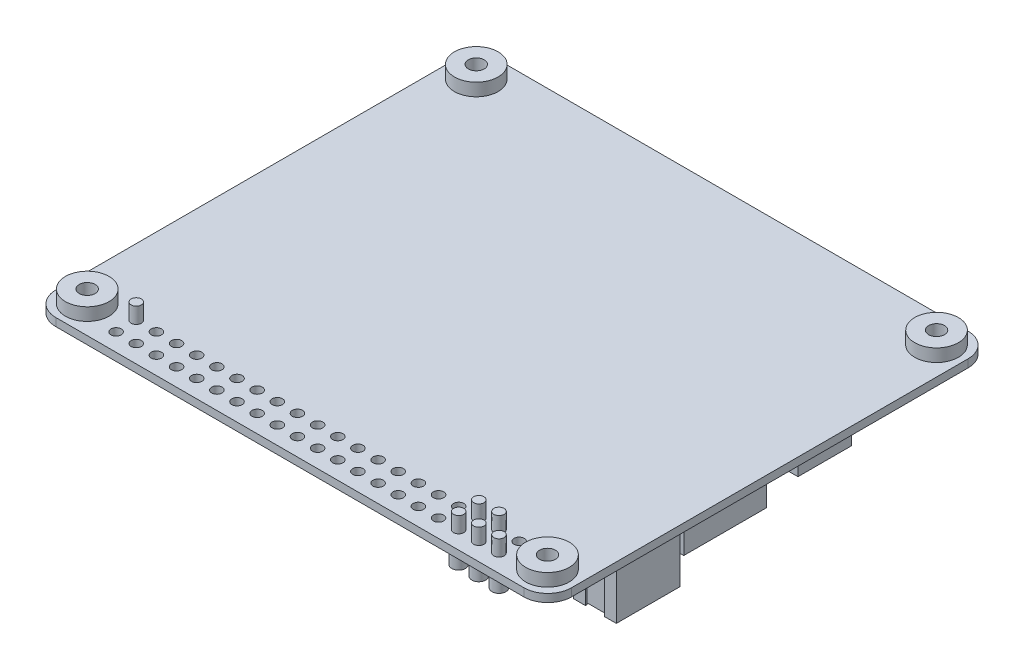
SolidWorks part; units mm, degrees
ref_plane "前视基准面" through (0, 0, 0) normal (0, 0, 1) x (1, 0, 0)
ref_plane "上视基准面" through (0, 0, 0) normal (0, 1, 0) x (1, 0, 0)
ref_plane "右视基准面" through (0, 0, 0) normal (1, 0, 0) x (0, 0, -1)
sketch "草图1" plane through (0, 0, 0) normal (0, 1, 0) x (1, 0, 0)
  line L1 (32.5, -28) -> (-32.5, -28)
  line L2 (32.5, -28) -> (32.5, 28)
  line L3 (32.5, 28) -> (-32.5, 28)
  line L4 (-32.5, -28) -> (-32.5, 28)
  line L5 (32.5, -28) -> (-32.5, 28) construction
  line L6 (32.5, 28) -> (-32.5, -28) construction
  point P0 (0, 0)
  dimension "D1" = 56
  dimension "D2" = 65
extrude "凸台-拉伸1" add sketch "草图1" along normal blind 1
fillet "圆角1" radius 3 4 edges at (32.5, 0.5, -28) (32.5, 0.5, 28) (-32.5, 0.5, 28) (-32.5, 0.5, -28)
sketch "草图2" plane through (0, 1, 0) normal (0, 1, 0) x (1, 0, 0)
  circle A0 centre (-29.0307, 24.5287) radius 2.75
  circle A1 centre (28.9808, 24.5287) radius 2.75
  circle A2 centre (-29.0307, -24.5065) radius 2.75
  circle A3 centre (28.9808, -24.5065) radius 2.75
  dimension "D1" = 5.5
extrude "凸台-拉伸2" add sketch "草图2" along normal blind 1.6
sketch "草图3" plane through (0, 2.6, 0) normal (0, 1, 0) x (1, 0, 0)
  circle A0 centre (-29.0307, 24.5287) radius 1
  circle A1 centre (28.9808, 24.5287) radius 1
  circle A2 centre (-29.0307, -24.5065) radius 1
  circle A3 centre (28.9808, -24.5065) radius 1
  dimension "D1" = 2
extrude "切除-拉伸1" cut sketch "草图3" against normal up to next
sketch "草图4" plane through (0, 0, 0) normal (0, -1, 0) x (1, 0, 0)
  line L0 (29.5, -28) -> (-29.5, -28) construction
  line L1 (25.5, -28) -> (16.5, -28)
  line L2 (25.5, -28) -> (25.5, -20.6)
  line L3 (25.5, -20.6) -> (16.5, -20.6)
  line L4 (16.5, -28) -> (16.5, -20.6)
  line L5 (32.5, 25) -> (32.5, -25) construction
  dimension "D1" = 7.4
  dimension "D2" = 9
  dimension "D3" = 7
extrude "凸台-拉伸3" add sketch "草图4" along normal blind 3.2
sketch "草图5" plane through (0, 0, -28) normal (0, 0, -1) x (-1, 0, 0)
  line L0 (-29.5, 0) -> (-25.5, 0) construction
  line L1 (-16.5, -3.2) -> (-25.5, -3.2)
  line L2 (-16.5, -3.2) -> (-16.5, 0)
  line L3 (-16.5, 0) -> (-25.5, 0)
  line L4 (-25.5, -3.2) -> (-25.5, 0)
  line L5 (-25.5, -3.2) -> (-25.5, 0) construction
extrude "凸台-拉伸4" add sketch "草图5" along normal blind 1
fillet "圆角3" radius 1 4 edges at (25.5, 0, -28.5) (25.5, -3.2, -24.8) (16.5, -3.2, -24.8) (16.5, 0, -28.5)
sketch "草图6" plane through (0, 0, 0) normal (0, -1, 0) x (1, 0, 0)
  line L0 (-32.5, -25) -> (-32.5, 25) construction
  circle A0 centre (-17.5, 0) radius 7
  dimension "D1" = 14
  dimension "D2" = 15
extrude "凸台-拉伸5" add sketch "草图6" along normal blind 2
sketch "草图8" plane through (0, 0, 0) normal (0, -1, 0) x (1, 0, 0)
  circle A0 centre (28.9808, 24.5065) radius 2
  circle A1 centre (28.9808, -24.5287) radius 2
  circle A2 centre (-29.0307, -24.5287) radius 2
  circle A3 centre (-29.0307, 24.5065) radius 2
  dimension "D1" = 4
extrude "凸台-拉伸6" add sketch "草图8" along normal blind 0.5
sketch "草图9" plane through (0, 0, 0) normal (0, 1, 0) x (1, 0, 0)
  circle A0 centre (-29.0307, 24.5287) radius 1
  circle A1 centre (28.9808, 24.5287) radius 1
  circle A2 centre (-29.0307, -24.5065) radius 1
  circle A3 centre (28.9808, -24.5065) radius 1
  circle A4 centre (28.9808, -24.5065) radius 2 construction
  circle A5 centre (28.9808, 24.5287) radius 2 construction
  circle A6 centre (-29.0307, -24.5065) radius 2 construction
  circle A7 centre (-29.0307, 24.5287) radius 2 construction
extrude "切除-拉伸2" cut sketch "草图9" against normal up to next
sketch "草图10" plane through (0, 0, -29) normal (0, 0, -1) x (-1, 0, 0)
  line L8 (-17.5, -0.2) -> (-24.5, -0.2)
  line L9 (-25.3, -1) -> (-25.3, -2.2)
  line L10 (-24.5, -3) -> (-17.5, -3)
  line L11 (-16.7, -2.2) -> (-16.7, -1)
  line L12 (-17.5, -0.2) -> (-24.5, -0.2)
  line L13 (-25.3, -1) -> (-25.3, -2.2)
  line L14 (-24.5, -3) -> (-17.5, -3)
  line L15 (-16.7, -2.2) -> (-16.7, -1)
  arc A8 (-24.5, -0.2) -> (-25.3, -1) centre (-24.5, -1) ccw
  arc A9 (-25.3, -2.2) -> (-24.5, -3) centre (-24.5, -2.2) ccw
  arc A10 (-17.5, -3) -> (-16.7, -2.2) centre (-17.5, -2.2) ccw
  arc A11 (-16.7, -1) -> (-17.5, -0.2) centre (-17.5, -1) ccw
  arc A12 (-24.5, -0.2) -> (-25.3, -1) centre (-24.5, -1) ccw
  arc A13 (-25.3, -2.2) -> (-24.5, -3) centre (-24.5, -2.2) ccw
  arc A14 (-17.5, -3) -> (-16.7, -2.2) centre (-17.5, -2.2) ccw
  arc A15 (-16.7, -1) -> (-17.5, -0.2) centre (-17.5, -1) ccw
  dimension "D1" = 0.2
extrude "切除-拉伸3" cut sketch "草图10" against normal blind 8
sketch "草图12" plane through (0, 0, 0) normal (0, -1, 0) x (1, 0, 0)
  line L0 (16.5, -28) -> (-29.5, -28) construction
  line L1 (-16.6, -28) -> (-23.9, -28)
  line L2 (-16.6, -28) -> (-16.6, -22.7)
  line L3 (-16.6, -22.7) -> (-23.9, -22.7)
  line L4 (-23.9, -28) -> (-23.9, -22.7)
  line L5 (-32.5, -25) -> (-32.5, 25) construction
  dimension "D1" = 7.3
  dimension "D2" = 8.6
  dimension "D3" = 5.3
extrude "凸台-拉伸8" add sketch "草图12" along normal blind 2.4
sketch "草图13" plane through (0, 0, -28) normal (0, 0, -1) x (-1, 0, 0)
  line L1 (23.9, -2.4) -> (16.6, -2.4)
  line L2 (23.9, -2.4) -> (23.9, 0)
  line L3 (23.9, 0) -> (16.6, 0)
  line L4 (16.6, -2.4) -> (16.6, 0)
extrude "凸台-拉伸9" add sketch "草图13" along normal up to surface (1 mm away) up to face at (21, -1.6, -29)
chamfer "倒角1" distance 0.4 angle 45 2 edges at (-16.6, -2.4, -25.85) (-23.9, -2.4, -25.85)
chamfer "倒角2" distance 1 angle 45 2 edges at (-16.6, 0, -28.5) (-23.9, 0, -28.5)
sketch "草图14" plane through (0, 0, -29) normal (0, 0, -1) x (-1, 0, 0)
  line L16 (22.8172, -0.2) -> (17.6828, -0.2)
  line L17 (17.6828, -0.2) -> (16.8, -1.0828)
  line L18 (16.8, -1.0828) -> (16.8, -1.9172)
  line L19 (16.8, -1.9172) -> (17.0828, -2.2)
  line L20 (17.0828, -2.2) -> (23.4172, -2.2)
  line L21 (23.4172, -2.2) -> (23.7, -1.9172)
  line L22 (23.7, -1.9172) -> (23.7, -1.0828)
  line L23 (23.7, -1.0828) -> (22.8172, -0.2)
  line L24 (22.8172, -0.2) -> (17.6828, -0.2)
  line L25 (17.6828, -0.2) -> (16.8, -1.0828)
  line L26 (16.8, -1.0828) -> (16.8, -1.9172)
  line L27 (16.8, -1.9172) -> (17.0828, -2.2)
  line L28 (17.0828, -2.2) -> (23.4172, -2.2)
  line L29 (23.4172, -2.2) -> (23.7, -1.9172)
  line L30 (23.7, -1.9172) -> (23.7, -1.0828)
  line L31 (23.7, -1.0828) -> (22.8172, -0.2)
  dimension "D1" = 0.2
extrude "切除-拉伸4" cut sketch "草图14" against normal blind 2.4
sketch "草图17" plane through (0, 0, -28) normal (0, 0, -1) x (-1, 0, 0)
  line L0 (23.9, -1) -> (23.9, 0)
  line L1 (23.9, 0) -> (22.9, 0)
  line L2 (22.9, 0) -> (23.9, -1)
  line L3 (16.6, 0) -> (17.6, 0)
  line L4 (17.6, 0) -> (16.6, -1)
  line L5 (16.6, -1) -> (16.6, 0) construction
  line L6 (16.6, -1) -> (16.6, 0)
extrude "切除-拉伸5" cut sketch "草图17" against normal up to surface (5.3 mm away) up to face at (-20.25, -1.4667, -22.7)
fillet "圆角4" radius 0.2 1 edges at (-17.5, -2, -7)
sketch "草图19" plane through (0, 0, 0) normal (0, -1, 0) x (1, 0, 0)
  line L0 (32.5, 25) -> (32.5, -25) construction
  line L1 (32, 18.85) -> (26.6, 18.85)
  line L2 (32, 18.85) -> (32, 10.85)
  line L3 (32, 10.85) -> (26.6, 10.85)
  line L4 (26.6, 18.85) -> (26.6, 10.85)
  line L5 (-29.5, 28) -> (29.5, 28) construction
  dimension "D1" = 8
  dimension "D2" = 5.4
  dimension "D3" = 0.5
  dimension "D4" = 9.15
extrude "凸台-拉伸13" add sketch "草图19" along normal blind 6.22
sketch "草图20" plane through (0, -6.22, 0) normal (0, -1, 0) x (1, 0, 0)
  line L0 (30.5, 18.85) -> (30.5, 18.65)
  line L1 (32, 18.85) -> (26.6, 18.85) construction
  line L2 (30.5, 18.65) -> (31.3599, 18.65)
  line L3 (31.3599, 18.65) -> (31.3599, 18.45)
  line L4 (31.3599, 18.45) -> (26.9378, 18.45)
  line L5 (26.9378, 18.45) -> (26.9378, 18.65)
  line L6 (26.9378, 18.65) -> (28.1, 18.65)
  line L7 (28.1, 18.65) -> (28.1, 18.85)
  line L8 (32, 18.85) -> (26.6, 18.85) construction
  line L9 (28.1, 18.85) -> (30.5, 18.85)
  line L10 (30.5, 10.85) -> (30.5, 11.05)
  line L11 (26.6, 10.85) -> (32, 10.85) construction
  line L12 (30.5, 11.05) -> (31.3599, 11.05)
  line L13 (31.3599, 11.05) -> (31.3599, 11.25)
  line L14 (31.3599, 11.25) -> (26.9378, 11.25)
  line L15 (26.9378, 11.25) -> (26.9378, 11.05)
  line L16 (26.9378, 11.05) -> (28.1, 11.05)
  line L17 (28.1, 11.05) -> (28.1, 10.85)
  line L18 (28.1, 10.85) -> (30.5, 10.85)
  line L19 (32, 10.85) -> (32, 18.85) construction
  line L20 (26.6, 18.85) -> (26.6, 10.85) construction
  dimension "D1" = 0.2
  dimension "D2" = 0.2
  dimension "D3" = 0.2
  dimension "D4" = 1.5
  dimension "D5" = 1.5
extrude "切除-拉伸6" cut sketch "草图20" against normal blind 6.22
sketch "草图21" plane through (0, -6.22, 0) normal (0, -1, 0) x (1, 0, 0)
  line L1 (31.3599, 18.0753) -> (26.9378, 18.0753)
  line L2 (31.3599, 18.0753) -> (31.3599, 11.6247)
  line L3 (31.3599, 11.6247) -> (26.9378, 11.6247)
  line L4 (26.9378, 18.0753) -> (26.9378, 11.6247)
  line L5 (31.3599, 18.0753) -> (26.9378, 11.6247) construction
  line L6 (31.3599, 11.6247) -> (26.9378, 18.0753) construction
  point P0 (29.1489, 14.85)
extrude "切除-拉伸7" cut sketch "草图21" against normal blind 5
sketch "草图22" plane through (0, -1.22, 0) normal (0, -1, 0) x (1, 0, 0)
  line L1 (29.5742, 16.0721) -> (29.0742, 16.0721)
  line L2 (29.5742, 16.0721) -> (29.5742, 15.5721)
  line L3 (29.5742, 15.5721) -> (29.0742, 15.5721)
  line L4 (29.0742, 16.0721) -> (29.0742, 15.5721)
  line L5 (29.5742, 16.0721) -> (29.0742, 15.5721) construction
  line L6 (29.5742, 15.5721) -> (29.0742, 16.0721) construction
  line L7 (29.5566, 14.331) -> (29.0566, 14.331)
  line L8 (29.5566, 14.331) -> (29.5566, 13.831)
  line L9 (29.5566, 13.831) -> (29.0566, 13.831)
  line L10 (29.0566, 14.331) -> (29.0566, 13.831)
  line L11 (29.5566, 14.331) -> (29.0566, 13.831) construction
  line L12 (29.5566, 13.831) -> (29.0566, 14.331) construction
  point P0 (29.3242, 15.8221)
  point P5 (29.3066, 14.081)
  dimension "D1" = 0.5
extrude "凸台-拉伸14" add sketch "草图22" along normal blind 5
chamfer "倒角3" distance 0.1 angle 45 8 edges at (29.3066, -6.22, 14.331) (29.5566, -6.22, 14.081) (29.3066, -6.22, 13.831) (29.0566, -6.22, 14.081) (29.3242, -6.22, 16.0721) (29.5742, -6.22, 15.8221) (29.3242, -6.22, 15.5721) (29.0742, -6.22, 15.8221)
sketch "草图26" plane through (0, 0, 0) normal (0, -1, 0) x (1, 0, 0)
  circle A0 centre (24.13, 25.77) radius 0.65
  circle A40 centre (21.59, 25.77) radius 0.65
  circle A41 centre (19.05, 25.77) radius 0.65
  circle A42 centre (16.51, 25.77) radius 0.65
  circle A43 centre (13.97, 25.77) radius 0.65
  circle A44 centre (11.43, 25.77) radius 0.65
  circle A45 centre (8.89, 25.77) radius 0.65
  circle A46 centre (6.35, 25.77) radius 0.65
  circle A47 centre (3.81, 25.77) radius 0.65
  circle A48 centre (1.27, 25.77) radius 0.65
  circle A49 centre (-1.27, 25.77) radius 0.65
  circle A50 centre (-3.81, 25.77) radius 0.65
  circle A51 centre (-6.35, 25.77) radius 0.65
  circle A52 centre (-8.89, 25.77) radius 0.65
  circle A53 centre (-11.43, 25.77) radius 0.65
  circle A54 centre (-13.97, 25.77) radius 0.65
  circle A55 centre (-16.51, 25.77) radius 0.65
  circle A56 centre (-19.05, 25.77) radius 0.65
  circle A57 centre (-21.59, 25.77) radius 0.65
  circle A58 centre (-24.13, 25.77) radius 0.65
  circle A59 centre (21.59, 23.23) radius 0.65
  circle A60 centre (19.05, 23.23) radius 0.65
  circle A61 centre (16.51, 23.23) radius 0.65
  circle A62 centre (13.97, 23.23) radius 0.65
  circle A63 centre (11.43, 23.23) radius 0.65
  circle A64 centre (8.89, 23.23) radius 0.65
  circle A65 centre (6.35, 23.23) radius 0.65
  circle A66 centre (3.81, 23.23) radius 0.65
  circle A67 centre (1.27, 23.23) radius 0.65
  circle A68 centre (-1.27, 23.23) radius 0.65
  circle A69 centre (-3.81, 23.23) radius 0.65
  circle A70 centre (-6.35, 23.23) radius 0.65
  circle A71 centre (-8.89, 23.23) radius 0.65
  circle A72 centre (-11.43, 23.23) radius 0.65
  circle A73 centre (-13.97, 23.23) radius 0.65
  circle A74 centre (-16.51, 23.23) radius 0.65
  circle A75 centre (-19.05, 23.23) radius 0.65
  circle A76 centre (-21.59, 23.23) radius 0.65
  circle A77 centre (-24.13, 23.23) radius 0.65
  circle A78 centre (24.13, 23.23) radius 0.65
  dimension "D1" = 1.3
  dimension "D2" = 20
  dimension "D3" = 2
extrude "切除-拉伸8" cut sketch "草图26" against normal up to surface (1 mm away) up to face at (28.9808, 1, 27.2565)
sketch "草图27" plane through (0, 0, 0) normal (0, -1, 0) x (1, 0, 0)
  circle A0 centre (24.13, 25.77) radius 1.15
  circle A1 centre (21.59, 25.77) radius 1.15
  circle A2 centre (21.59, 23.23) radius 1.15
  circle A3 centre (19.05, 25.77) radius 1.15
  circle A4 centre (19.05, 23.23) radius 1.15
  circle A5 centre (13.97, 23.23) radius 1.15
  circle A6 centre (21.59, 25.77) radius 0.65 construction
  point P6 (0, 0)
  point P18 (-24.13, 23.23)
  point P21 (0, 0)
  point P22 (11.2753, 22.0258)
  point P23 (13.97, 23.23)
  dimension "D1" = 2.3
extrude "凸台-拉伸18" add sketch "草图27" along normal blind 0.8
sketch "草图28" plane through (0, -0.8, 0) normal (0, -1, 0) x (-1, 0, 0)
  circle A0 centre (-24.13, -25.77) radius 0.875
  circle A1 centre (-21.59, -25.77) radius 0.875
  circle A2 centre (-19.05, -23.23) radius 0.875
  circle A3 centre (-21.59, -23.23) radius 0.875
  circle A4 centre (-19.05, -25.77) radius 0.875
  circle A5 centre (-13.97, -23.23) radius 0.875
  dimension "D1" = 1.75
extrude "凸台-拉伸19" add sketch "草图28" along normal blind 2
sketch "草图29" plane through (0, 0, 0) normal (0, 1, 0) x (1, 0, 0)
  circle A0 centre (19.05, -23.23) radius 0.65 construction
  circle A1 centre (19.05, -25.77) radius 0.65 construction
  circle A2 centre (21.59, -23.23) radius 0.65 construction
  circle A4 centre (24.13, -25.77) radius 0.65 construction
  circle A5 centre (-24.13, -23.23) radius 0.65 construction
  circle A6 centre (19.05, -23.23) radius 0.65
  circle A7 centre (19.05, -25.77) radius 0.65
  circle A8 centre (21.59, -23.23) radius 0.65
  circle A9 centre (21.59, -25.77) radius 0.65
  circle A10 centre (24.13, -25.77) radius 0.65
  circle A11 centre (-24.13, -23.23) radius 0.65
  circle A12 centre (21.59, -25.77) radius 0.65 construction
extrude "凸台-拉伸20" add sketch "草图29" along normal blind 3
sketch "草图30" plane through (0, 0, -28) normal (0, 0, -1) x (-1, 0, 0)
  line L0 (-16.5, 0) -> (-17.5, 0)
  line L1 (-16.5, 0) -> (-16.5, -1) construction
  line L2 (-16.5, 0) -> (-16.5, -1)
  line L3 (-25.5, 0) -> (-24.5, 0)
  line L4 (-25.5, -1) -> (-25.5, 0) construction
  line L5 (-25.5, -1) -> (-25.5, 0)
  arc A0 (-16.5, -1) -> (-17.5, 0) centre (-17.5, -1) ccw construction
  arc A1 (-16.5, -1) -> (-17.5, 0) centre (-17.5, -1) ccw
  arc A2 (-24.5, 0) -> (-25.5, -1) centre (-24.5, -1) ccw construction
  arc A3 (-24.5, 0) -> (-25.5, -1) centre (-24.5, -1) ccw
extrude "切除-拉伸9" cut sketch "草图30" against normal up to next
sketch "草图31" plane through (0, 0, 0) normal (0, -1, 0) x (1, 0, 0)
  line L0 (-269.1222, 141.019) -> (182.8778, 141.019) construction
  line L1 (24.5, -20.6) -> (17.5, -20.6) construction
  line L2 (31.459, 9.8102) -> (19.8345, 9.8102)
  line L3 (31.459, 9.8102) -> (31.459, -0.6109)
  line L4 (31.459, -0.6109) -> (19.8345, -0.6109)
  line L5 (19.8345, 9.8102) -> (19.8345, -0.6109)
  line L6 (31.459, -1.1785) -> (28.1669, -1.1785)
  line L7 (31.459, -1.1785) -> (31.459, -4.516)
  line L8 (31.459, -4.516) -> (28.1669, -4.516)
  line L9 (28.1669, -1.1785) -> (28.1669, -4.516)
  line L10 (27.1452, -1.4056) -> (22.332, -1.4056)
  line L11 (27.1452, -1.4056) -> (27.1452, -4.1981)
  line L12 (27.1452, -4.1981) -> (22.332, -4.1981)
  line L13 (22.332, -1.4056) -> (22.332, -4.1981)
  line L14 (31.0503, -4.9928) -> (23.558, -4.9928)
  line L15 (31.0503, -4.9928) -> (31.0503, -11.7586)
  line L16 (31.0503, -11.7586) -> (23.558, -11.7586)
  line L17 (23.558, -4.9928) -> (23.558, -11.7586)
  line L18 (31.459, -13.2884) -> (30.0812, -13.2884)
  line L19 (31.459, -13.2884) -> (31.459, -15.1195)
  line L20 (31.459, -15.1195) -> (30.0812, -15.1195)
  line L21 (30.0812, -13.2884) -> (30.0812, -15.1195)
  line L22 (29.3946, -12.2203) -> (27.6398, -12.2203)
  line L23 (29.3946, -12.2203) -> (29.3946, -13.0596)
  line L24 (29.3946, -13.0596) -> (27.6398, -13.0596)
  line L25 (27.6398, -12.2203) -> (27.6398, -13.0596)
  line L26 (25.1221, -19.2775) -> (23.024, -19.2775)
  line L27 (25.1221, -19.2775) -> (25.1221, -20.6)
  line L28 (25.1221, -20.6) -> (23.024, -20.6)
  line L29 (23.024, -19.2775) -> (23.024, -20.6)
  line L30 (24.5, -20.6) -> (17.5, -20.6) construction
  line L31 (21.8033, -19.2775) -> (20.7352, -19.2775)
  line L32 (21.8033, -19.2775) -> (21.8033, -20.6)
  line L33 (21.8033, -20.6) -> (20.7352, -20.6)
  line L34 (20.7352, -19.2775) -> (20.7352, -20.6)
  line L35 (-4.9095, -24.5987) -> (-6.2095, -24.5987)
  line L36 (20.2393, -19.2775) -> (19.2474, -19.2775)
  line L37 (20.2393, -19.2775) -> (20.2393, -20.6)
  line L38 (20.2393, -20.6) -> (19.2474, -20.6)
  line L39 (19.2474, -19.2775) -> (19.2474, -20.6)
  line L40 (25.1221, -17.065) -> (23.024, -17.065)
  line L41 (25.1221, -17.065) -> (25.1221, -18.5146)
  line L42 (25.1221, -18.5146) -> (23.024, -18.5146)
  line L43 (23.024, -17.065) -> (23.024, -18.5146)
  line L44 (21.2692, -13.0596) -> (18.103, -13.0596)
  line L45 (21.2692, -13.0596) -> (21.2692, -16.3402)
  line L46 (21.2692, -16.3402) -> (18.103, -16.3402)
  line L47 (18.103, -13.0596) -> (18.103, -16.3402)
  line L48 (19.2474, -0.6109) -> (18.4047, -0.6109)
  line L49 (19.2474, -0.6109) -> (19.2474, -2.216)
  line L50 (19.2474, -2.216) -> (18.4047, -2.216)
  line L51 (18.4047, -0.6109) -> (18.4047, -2.216)
  line L52 (13.1588, -24.973) -> (8.3931, -24.973)
  line L53 (13.1588, -24.973) -> (13.1588, -27.3005)
  line L54 (13.1588, -27.3005) -> (8.3931, -27.3005)
  line L55 (8.3931, -24.973) -> (8.3931, -27.3005)
  line L56 (4.6988, -24.973) -> (0, -24.973)
  line L57 (4.6988, -24.973) -> (4.6988, -27.3005)
  line L58 (4.6988, -27.3005) -> (0, -27.3005)
  line L59 (0, -24.973) -> (0, -27.3005)
  line L60 (8.3931, 15.9758) -> (4.9221, 15.9758)
  line L61 (8.3931, 15.9758) -> (8.3931, 13.2491)
  line L62 (8.3931, 13.2491) -> (4.9221, 13.2491)
  line L63 (4.9221, 15.9758) -> (4.9221, 13.2491)
  line L64 (8.3931, 11.7221) -> (4.9221, 11.7221)
  line L65 (8.3931, 11.7221) -> (8.3931, 9.0318)
  line L66 (8.3931, 9.0318) -> (4.9221, 9.0318)
  line L67 (4.9221, 11.7221) -> (4.9221, 9.0318)
  line L68 (9.6847, 6.3051) -> (5.9037, 6.3051)
  line L69 (9.6847, 6.3051) -> (9.6847, 1.4698)
  line L70 (9.6847, 1.4698) -> (5.9037, 1.4698)
  line L71 (5.9037, 6.3051) -> (5.9037, 1.4698)
  line L80 (-1.5572, -24.1659) -> (-3.3676, -24.1659)
  line L81 (-1.5572, -24.1659) -> (-1.5572, -27.3005)
  line L82 (-1.5572, -27.3005) -> (-3.3676, -27.3005)
  line L83 (-3.3676, -24.1659) -> (-3.3676, -27.3005)
  line L88 (-4.9095, -24.5987) -> (-4.9095, -26.7453)
  line L89 (-4.9095, -26.7453) -> (-6.2095, -26.7453)
  line L90 (-6.2095, -24.5987) -> (-6.2095, -26.7453)
  line L92 (-7.0018, -24.5987) -> (-8.3018, -24.5987)
  line L93 (-7.0018, -24.5987) -> (-7.0018, -26.7453)
  line L94 (-7.0018, -26.7453) -> (-8.3018, -26.7453)
  line L95 (-8.3018, -24.5987) -> (-8.3018, -26.7453)
  line L96 (-9.1473, -24.5987) -> (-10.4473, -24.5987)
  line L97 (-9.1473, -24.5987) -> (-9.1473, -26.7453)
  line L98 (-9.1473, -26.7453) -> (-10.4473, -26.7453)
  line L99 (-10.4473, -24.5987) -> (-10.4473, -26.7453)
  line L100 (-11.2125, -24.5987) -> (-12.5125, -24.5987)
  line L101 (-11.2125, -24.5987) -> (-11.2125, -26.7453)
  line L102 (-11.2125, -26.7453) -> (-12.5125, -26.7453)
  line L103 (-12.5125, -24.5987) -> (-12.5125, -26.7453)
  line L104 (-13.2578, -24.5987) -> (-14.5578, -24.5987)
  line L105 (-13.2578, -24.5987) -> (-13.2578, -26.7453)
  line L106 (-13.2578, -26.7453) -> (-14.5578, -26.7453)
  line L107 (-14.5578, -24.5987) -> (-14.5578, -26.7453)
  line L108 (0.6545, -17.8156) -> (-0.8398, -17.8156)
  line L109 (0.6545, -17.8156) -> (0.6545, -19.6835)
  line L110 (0.6545, -19.6835) -> (-0.8398, -19.6835)
  line L111 (-0.8398, -17.8156) -> (-0.8398, -19.6835)
  line L112 (-9.9754, -18.0873) -> (-11.6734, -18.0873)
  line L113 (-9.9754, -18.0873) -> (-9.9754, -18.9703)
  line L114 (-9.9754, -18.9703) -> (-11.6734, -18.9703)
  line L115 (-11.6734, -18.0873) -> (-11.6734, -18.9703)
  line L116 (-1.2233, 3.594) -> (-2.668, 3.594)
  line L117 (-1.2233, 3.594) -> (-1.2233, 1.8282)
  line L118 (-1.2233, 1.8282) -> (-2.668, 1.8282)
  line L119 (-2.668, 3.594) -> (-2.668, 1.8282)
  line L120 (-2.2552, -2.7581) -> (-3.1725, -2.7581)
  line L121 (-2.2552, -2.7581) -> (-2.2552, -4.516)
  line L122 (-2.2552, -4.516) -> (-3.1725, -4.516)
  line L123 (-3.1725, -2.7581) -> (-3.1725, -4.516)
  line L124 (-4.6401, -2.7581) -> (-5.5344, -2.7581)
  line L125 (-4.6401, -2.7581) -> (-4.6401, -4.516)
  line L126 (-4.6401, -4.516) -> (-5.5344, -4.516)
  line L127 (-5.5344, -2.7581) -> (-5.5344, -4.516)
  line L128 (-6.2095, -3.8955) -> (-7.2269, -3.8955)
  line L129 (-6.2095, -3.8955) -> (-6.2095, -5.7277)
  line L130 (-6.2095, -5.7277) -> (-7.2269, -5.7277)
  line L131 (-7.2269, -3.8955) -> (-7.2269, -5.7277)
  line L132 (-7.6341, -3.8955) -> (-8.5039, -3.8955)
  line L133 (-7.6341, -3.8955) -> (-7.6341, -5.7277)
  line L134 (-7.6341, -5.7277) -> (-8.5039, -5.7277)
  line L135 (-8.5039, -3.8955) -> (-8.5039, -5.7277)
  line L136 (-8.8925, -3.8955) -> (-9.8179, -3.8955)
  line L137 (-8.8925, -3.8955) -> (-8.8925, -5.7277)
  line L138 (-8.8925, -5.7277) -> (-9.8179, -5.7277)
  line L139 (-9.8179, -3.8955) -> (-9.8179, -5.7277)
  line L140 (-10.188, -3.8955) -> (-11.2125, -3.8955)
  line L141 (-10.188, -3.8955) -> (-10.188, -5.7277)
  line L142 (-10.188, -5.7277) -> (-11.2125, -5.7277)
  line L143 (-11.2125, -3.8955) -> (-11.2125, -5.7277)
  line L144 (12.5814, 9.3712) -> (10.7759, 9.3712)
  line L145 (12.5814, 9.3712) -> (12.5814, 8.2563)
  line L146 (12.5814, 8.2563) -> (10.7759, 8.2563)
  line L147 (10.7759, 9.3712) -> (10.7759, 8.2563)
  line L148 (11.6787, 7.8846) -> (10.0309, 7.8846)
  line L149 (11.6787, 7.8846) -> (11.6787, 6.9555)
  line L150 (11.6787, 6.9555) -> (10.0309, 6.9555)
  line L151 (10.0309, 7.8846) -> (10.0309, 6.9555)
  line L152 (12.1492, 6.3051) -> (10.4025, 6.3051)
  line L153 (12.1492, 6.3051) -> (12.1492, 5.2831)
  line L154 (12.1492, 5.2831) -> (10.4025, 5.2831)
  line L155 (10.4025, 6.3051) -> (10.4025, 5.2831)
  line L156 (12.1492, 1.4698) -> (10.4025, 1.4698)
  line L157 (12.1492, 1.4698) -> (12.1492, 0.5632)
  line L158 (12.1492, 0.5632) -> (10.4025, 0.5632)
  line L159 (10.4025, 1.4698) -> (10.4025, 0.5632)
  line L160 (11.6787, -0.3659) -> (10.4025, -0.3659)
  line L161 (11.6787, -0.3659) -> (11.6787, -2.216)
  line L162 (11.6787, -2.216) -> (10.4025, -2.216)
  line L163 (10.4025, -0.3659) -> (10.4025, -2.216)
  line L164 (10.0309, -0.3659) -> (8.9159, -0.3659)
  line L165 (10.0309, -0.3659) -> (10.0309, -2.216)
  line L166 (10.0309, -2.216) -> (8.9159, -2.216)
  line L167 (8.9159, -0.3659) -> (8.9159, -2.216)
  line L168 (8.9159, 7.8846) -> (7.2064, 7.8846)
  line L169 (8.9159, 7.8846) -> (8.9159, 6.9555)
  line L170 (8.9159, 6.9555) -> (7.2064, 6.9555)
  line L171 (7.2064, 7.8846) -> (7.2064, 6.9555)
  line L172 (6.5746, 0.5632) -> (5.6083, 0.5632)
  line L173 (6.5746, 0.5632) -> (6.5746, -0.9234)
  line L174 (6.5746, -0.9234) -> (5.6083, -0.9234)
  line L175 (5.6083, 0.5632) -> (5.6083, -0.9234)
  line L176 (4.9221, 1.8282) -> (3.1926, 1.8282)
  line L177 (4.9221, 1.8282) -> (4.9221, 1.0165)
  line L178 (4.9221, 1.0165) -> (3.1926, 1.0165)
  line L179 (3.1926, 1.8282) -> (3.1926, 1.0165)
  line L180 (4.9221, 0.2287) -> (4.0574, 0.2287)
  line L181 (4.9221, 0.2287) -> (4.9221, -1.4056)
  line L182 (4.9221, -1.4056) -> (4.0574, -1.4056)
  line L183 (4.0574, 0.2287) -> (4.0574, -1.4056)
  line L184 (3.6386, 0.2287) -> (2.7466, 0.2287)
  line L185 (3.6386, 0.2287) -> (3.6386, -1.4056)
  line L186 (3.6386, -1.4056) -> (2.7466, -1.4056)
  line L187 (2.7466, 0.2287) -> (2.7466, -1.4056)
  line L188 (5.3755, 3.0635) -> (4.4942, 3.0635)
  line L189 (5.3755, 3.0635) -> (5.3755, 4.8142)
  line L190 (1.6317, 2.3471) -> (3.1926, 2.3471)
  line L191 (1.6317, 2.3471) -> (1.6317, 3.3134)
  line L192 (1.6317, 3.3134) -> (3.1926, 3.3134)
  line L193 (3.1926, 2.3471) -> (3.1926, 3.3134)
  line L194 (5.3755, 4.8142) -> (4.4942, 4.8142)
  line L195 (4.4942, 3.0635) -> (4.4942, 4.8142)
  line L196 (-26.4365, 18.1309) -> (-28.123, 18.1309)
  line L197 (-26.4365, 18.1309) -> (-26.4365, 14.8151)
  line L198 (-26.4365, 14.8151) -> (-28.123, 14.8151)
  line L199 (-28.123, 18.1309) -> (-28.123, 14.8151)
  line L200 (-14.8746, -12.2203) -> (-16.6449, -12.2203)
  line L201 (-14.8746, -12.2203) -> (-14.8746, -13.1933)
  line L202 (-14.8746, -13.1933) -> (-16.6449, -13.1933)
  line L203 (-16.6449, -12.2203) -> (-16.6449, -13.1933)
  line L204 (-14.2012, -14.6161) -> (-17.3617, -14.6161)
  line L205 (-14.2012, -14.6161) -> (-14.2012, -16.5384)
  line L206 (-14.2012, -16.5384) -> (-17.3617, -16.5384)
  line L207 (-17.3617, -14.6161) -> (-17.3617, -16.5384)
  line L208 (-17.8504, -16.6905) -> (-18.8061, -16.6905)
  line L209 (-17.8504, -16.6905) -> (-17.8504, -18.363)
  line L210 (-17.8504, -18.363) -> (-18.8061, -18.363)
  line L211 (-18.8061, -16.6905) -> (-18.8061, -18.363)
  line L212 (-19.4653, -16.6905) -> (-20.411, -16.6905)
  line L213 (-19.4653, -16.6905) -> (-19.4653, -18.363)
  line L214 (-19.4653, -18.363) -> (-20.411, -18.363)
  line L215 (-20.411, -16.6905) -> (-20.411, -18.363)
  line L216 (-21.0003, -16.6905) -> (-21.9533, -16.6905)
  line L217 (-21.0003, -16.6905) -> (-21.0003, -18.363)
  line L218 (-21.0003, -18.363) -> (-21.9533, -18.363)
  line L219 (-21.9533, -16.6905) -> (-21.9533, -18.363)
  line L220 (-22.4419, -16.6905) -> (-23.3932, -16.6905)
  line L221 (-22.4419, -16.6905) -> (-22.4419, -18.363)
  line L222 (-22.4419, -18.363) -> (-23.3932, -18.363)
  line L223 (-23.3932, -16.6905) -> (-23.3932, -18.363)
  line L224 (-19.5638, -11.4061) -> (-22.1884, -11.4061)
  line L225 (-19.5638, -11.4061) -> (-19.5638, -14.9023)
  line L226 (-19.5638, -14.9023) -> (-22.1884, -14.9023)
  line L227 (-22.1884, -11.4061) -> (-22.1884, -14.9023)
  dimension "D1" = 1.3
extrude "凸台-拉伸21" add sketch "草图31" along normal blind 0.6
sketch "草图32" plane through (0, -0.6, 0) normal (0, -1, 0) x (1, 0, 0)
  line L4 (31.459, -0.6109) -> (31.459, 9.8102)
  line L5 (31.459, 9.8102) -> (19.8345, 9.8102)
  line L6 (19.8345, 9.8102) -> (19.8345, -0.6109)
  line L7 (19.8345, -0.6109) -> (31.459, -0.6109)
  line L8 (31.459, -0.6109) -> (31.459, 9.8102)
  line L9 (31.459, 9.8102) -> (19.8345, 9.8102)
  line L10 (19.8345, 9.8102) -> (19.8345, -0.6109)
  line L11 (19.8345, -0.6109) -> (31.459, -0.6109)
  dimension "D1" = 0
extrude "凸台-拉伸22" add sketch "草图32" along normal blind 3
sketch "草图33" plane through (0, -0.6, 0) normal (0, -1, 0) x (1, 0, 0)
  line L4 (31.0503, -11.7586) -> (31.0503, -4.9928)
  line L5 (31.0503, -4.9928) -> (23.558, -4.9928)
  line L6 (23.558, -4.9928) -> (23.558, -11.7586)
  line L7 (23.558, -11.7586) -> (31.0503, -11.7586)
  line L8 (31.0503, -11.7586) -> (31.0503, -4.9928)
  line L9 (31.0503, -4.9928) -> (23.558, -4.9928)
  line L10 (23.558, -4.9928) -> (23.558, -11.7586)
  line L11 (23.558, -11.7586) -> (31.0503, -11.7586)
  dimension "D1" = 0
extrude "凸台-拉伸23" add sketch "草图33" along normal blind 2
sketch "草图34" plane through (0, -0.6, 0) normal (0, -1, 0) x (1, 0, 0)
  line L0 (13.1588, -27.3005) -> (13.1588, -24.973) construction
  line L1 (13.1588, -24.973) -> (8.3931, -24.973) construction
  line L2 (8.3931, -24.973) -> (8.3931, -27.3005) construction
  line L3 (8.3931, -27.3005) -> (13.1588, -27.3005) construction
  line L4 (4.6988, -27.3005) -> (4.6988, -24.973) construction
  line L5 (4.6988, -24.973) -> (0, -24.973) construction
  line L6 (0, -24.973) -> (0, -27.3005) construction
  line L7 (0, -27.3005) -> (4.6988, -27.3005) construction
  line L8 (13.1588, -27.3005) -> (13.1588, -24.973)
  line L9 (13.1588, -24.973) -> (8.3931, -24.973)
  line L10 (8.3931, -24.973) -> (8.3931, -27.3005)
  line L11 (8.3931, -27.3005) -> (13.1588, -27.3005)
  line L12 (4.6988, -27.3005) -> (4.6988, -24.973)
  line L13 (4.6988, -24.973) -> (0, -24.973)
  line L14 (0, -24.973) -> (0, -27.3005)
  line L15 (0, -27.3005) -> (4.6988, -27.3005)
extrude "凸台-拉伸24" add sketch "草图34" along normal blind 1
sketch "草图35" plane through (0, 0, -27.3005) normal (0, 0, -1) x (-1, 0, 0)
  line L4 (-8.3931, -1.6) -> (-13.1588, -1.6) construction
  line L5 (-1.1494, -1.3039) -> (-3.5494, -1.3039)
  line L6 (-1.1494, -1.3039) -> (-1.1494, -0.2961)
  line L7 (-1.1494, -0.2961) -> (-3.5494, -0.2961)
  line L8 (-3.5494, -1.3039) -> (-3.5494, -0.2961)
  line L9 (-1.1494, -1.3039) -> (-3.5494, -0.2961) construction
  line L10 (-1.1494, -0.2961) -> (-3.5494, -1.3039) construction
  line L11 (-9.5759, -1.3039) -> (-11.9759, -1.3039)
  line L12 (-9.5759, -1.3039) -> (-9.5759, -0.2961)
  line L13 (-9.5759, -0.2961) -> (-11.9759, -0.2961)
  line L14 (-11.9759, -1.3039) -> (-11.9759, -0.2961)
  line L15 (-9.5759, -1.3039) -> (-11.9759, -0.2961) construction
  line L16 (-9.5759, -0.2961) -> (-11.9759, -1.3039) construction
  line L17 (0, -1.6) -> (-4.6988, -1.6) construction
  point P0 (-10.7759, -0.8)
  point P2 (-2.3494, -0.8)
  point P10 (0, 0)
  point P13 (-10.7759, -1.6)
  point P14 (0, 0)
  point P17 (-2.3494, -1.6)
  dimension "D1" = 2.4
extrude "凸台-拉伸25" add sketch "草图35" along normal blind 0.8
